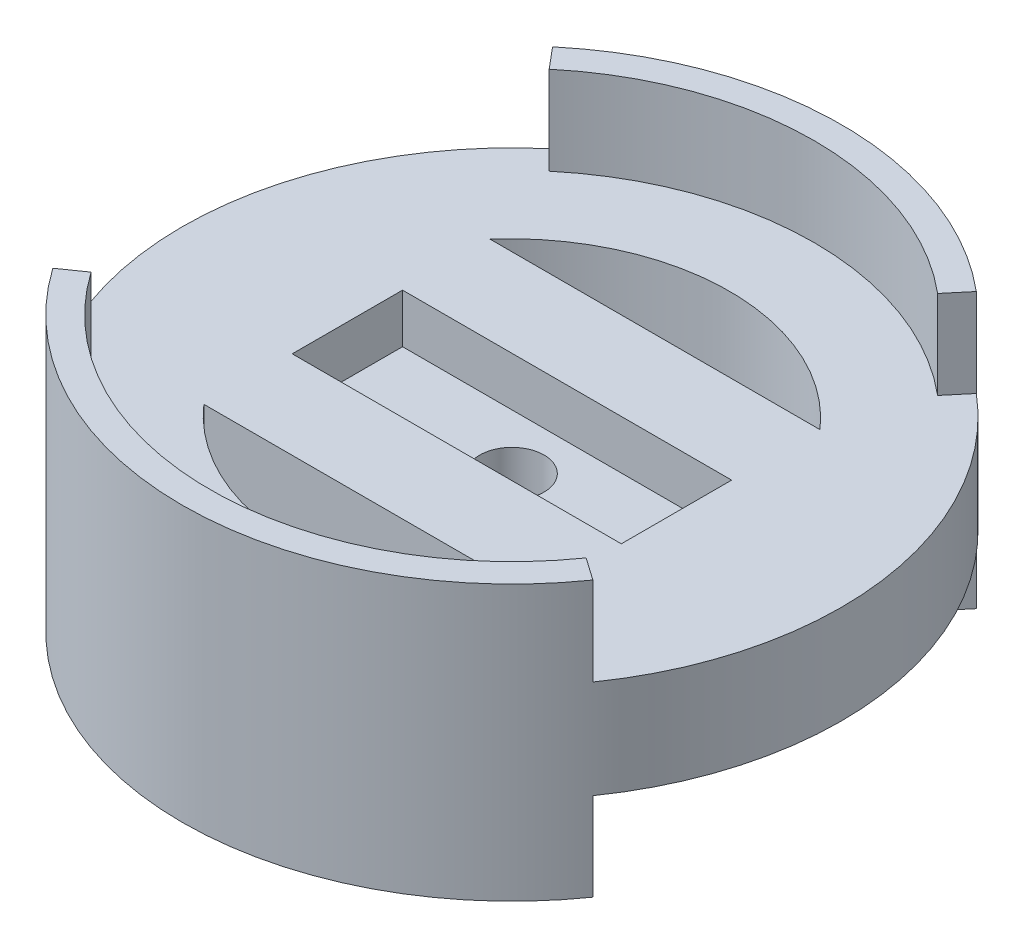
SolidWorks part; units mm, degrees
ref_plane "Front Plane" through (0, 0, 0) normal (0, 0, 1) x (1, 0, 0)
ref_plane "Top Plane" through (0, 0, 0) normal (0, 1, 0) x (1, 0, 0)
ref_plane "Right Plane" through (0, 0, 0) normal (1, 0, 0) x (0, 0, -1)
sketch "Sketch1" plane through (0, 0, 0) normal (0, 1, 0) x (1, 0, 0)
  line L1 (19.0182, -6.3754) -> (-19.0183, -6.3754)
  line L2 (19.0182, -6.3754) -> (19.0182, 6.3754)
  line L3 (19.0182, 6.3754) -> (-19.0183, 6.3754)
  line L4 (-19.0183, -6.3754) -> (-19.0183, 6.3754)
  line L5 (19.0182, -6.3754) -> (-19.0183, 6.3754) construction
  line L6 (19.0182, 6.3754) -> (-19.0183, -6.3754) construction
  circle A0 centre (0, 0) radius 38.1
  circle A1 centre (0, 0) radius 3.7147
  dimension "D1" = 76.2
  dimension "D4" = 7.4295
  dimension "D2" = 38.0365
  dimension "D3" = 12.7508
extrude "Boss-Extrude1" add sketch "Sketch1" along normal blind 5.6642 contours A0 L1 L4 L3 L2 region at (-37.0224, 0, 0)
extrude "Boss-Extrude2" add sketch "Sketch1<3>" against normal blind 5.715 contours A0 L1 L4 L3 L2 | L4 L1 L2 L3 A1 region at (0, 0, 5.9742) region at (-37.0224, 0, 0)
sketch "Sketch1<3>" plane through (0, 0, 0) normal (0, 1, 0) x (1, 0, 0) same geometry as "Sketch1"
sketch "Sketch2" plane through (0, 0, 0) normal (0, 1, 0) x (1, 0, 0)
  line L2 (0, 38.1) -> (0, -38.1) construction
  line L5 (-28.6089, -20.0322) -> (-31.2097, -21.8533)
  line L10 (28.6089, -20.0322) -> (31.2097, -21.8533)
  line L11 (-22.4494, 26.7541) -> (-24.4902, 29.1863)
  line L12 (22.4494, 26.7541) -> (24.4902, 29.1863)
  circle A9 centre (0, 0) radius 38.1
  arc A10 (-28.6089, -20.0322) -> (28.6089, -20.0322) centre (0, 0) ccw
  arc A11 (22.4494, 26.7541) -> (-22.4494, 26.7541) centre (0, 0) ccw
  point P7 (0, 0)
  point P17 (0, 0)
  point P20 (0, 0)
  dimension "D1" = 76.2
  dimension "D2" = 69.85
  dimension "D3" = 110
  dimension "D4" = 80
  dimension "D5" = 46.7863
  dimension "D6" = 44.8987
extrude "Boss-Extrude3" add sketch "Sketch2" along normal mid plane 31.75 contours A10 L2 A9 L10 | L2 A10 L5 A9 | L2 A9 L11 A11 | A9 L2 A11 L12 region at (12.2437, 0, -33.6392) region at (-12.2437, 0, -33.6392) region at (16.2299, 0, 31.1774) region at (-16.2299, 0, 31.1774)
sketch "Sketch3" plane through (0, 5.6642, 0) normal (0, 1, 0) x (1, 0, 0)
  line L0 (-19.0754, 16.5354) -> (19.0754, 16.5354)
  line L1 (19.0183, 0) -> (-19.0183, 0) construction
  line L2 (-19.0183, -6.3754) -> (-19.0183, 6.3754) construction
  line L3 (19.0182, 6.3754) -> (-19.0183, 6.3754) construction
  line L4 (0, 0) -> (0, 25.1637) construction
  line L5 (-19.0754, -16.5354) -> (19.0754, -16.5354)
  arc A4 (-19.0754, 16.5354) -> (19.0754, 16.5354) centre (0, -0.2363) cw
  arc A5 (-19.0754, -16.5354) -> (19.0754, -16.5354) centre (0, 0.2363) ccw
  point P8 (0, 0)
  dimension "D3" = 25.4
  dimension "D1" = 38.1508
  dimension "D2" = 10.16
extrude "Cut-Extrude2" cut sketch "Sketch3" against normal through all
